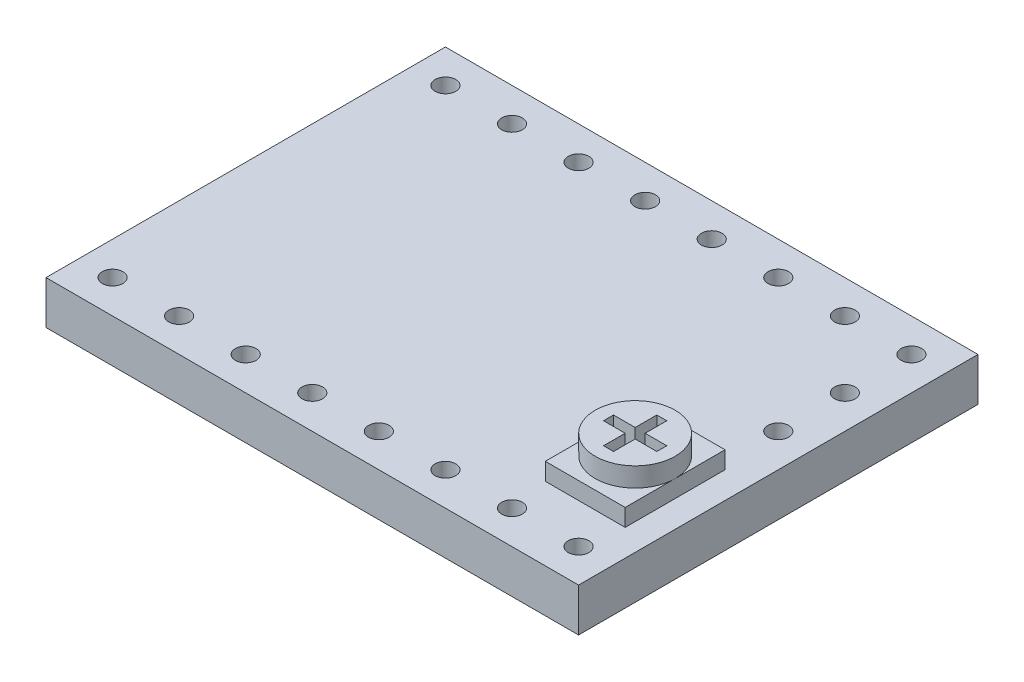
SolidWorks part; units mm, degrees
ref_plane "Front Plane" through (0, 0, 0) normal (0, 0, 1) x (1, 0, 0)
ref_plane "Top Plane" through (0, 0, 0) normal (0, 1, 0) x (1, 0, 0)
ref_plane "Right Plane" through (0, 0, 0) normal (1, 0, 0) x (0, 0, -1)
sketch "Sketch1" plane through (0, 0, 0) normal (0, 1, 0) x (1, 0, 0)
  line L1 (-10.16, -7.62) -> (10.16, -7.62)
  line L2 (-10.16, -7.62) -> (-10.16, 7.62)
  line L3 (-10.16, 7.62) -> (10.16, 7.62)
  line L4 (10.16, -7.62) -> (10.16, 7.62)
  line L5 (-10.16, -7.62) -> (10.16, 7.62) construction
  line L6 (-10.16, 7.62) -> (10.16, -7.62) construction
  point P0 (0, 0)
  dimension "D1" = 20.32
  dimension "D2" = 15.24
extrude "Boss-Extrude1" add sketch "Sketch1" along normal blind 1.651
sketch "Sketch3" plane through (0, 1.651, 0) normal (0, 1, 0) x (1, 0, 0)
  line L0 (10.16, -7.62) -> (10.16, 7.62) construction
  line L1 (6.096, -4.826) -> (9.144, -4.826)
  line L2 (6.096, -4.826) -> (6.096, -1.016)
  line L3 (6.096, -1.016) -> (9.144, -1.016)
  line L4 (9.144, -4.826) -> (9.144, -1.016)
  line L5 (-10.16, -7.62) -> (10.16, -7.62) construction
  dimension "D1" = 3.048
  dimension "D2" = 1.016
  dimension "D3" = 2.794
  dimension "D4" = 3.81
extrude "Boss-Extrude3" add sketch "Sketch3" along normal offset from surface (0.6604 mm away) 2.3114 up to face at (0, 0, 0)
sketch "Sketch4" plane through (0, 2.3114, 0) normal (0, 1, 0) x (1, 0, 0)
  line L0 (6.096, -4.826) -> (9.144, -1.016) construction
  line L1 (7.8105, -2.7305) -> (8.636, -2.7305)
  line L2 (7.4295, -3.937) -> (7.8105, -3.937)
  line L3 (7.4295, -3.937) -> (7.4295, -3.1115)
  line L4 (7.4295, -1.905) -> (7.8105, -1.905)
  line L5 (7.8105, -3.937) -> (7.8105, -3.1115)
  line L6 (7.4295, -3.937) -> (7.8105, -1.905) construction
  line L7 (7.4295, -1.905) -> (7.8105, -3.937) construction
  line L8 (6.604, -2.7305) -> (7.4295, -2.7305)
  line L9 (6.604, -2.7305) -> (6.604, -3.1115)
  line L10 (6.604, -3.1115) -> (7.4295, -3.1115)
  line L11 (8.636, -2.7305) -> (8.636, -3.1115)
  line L12 (6.604, -2.7305) -> (8.636, -3.1115) construction
  line L13 (6.604, -3.1115) -> (8.636, -2.7305) construction
  line L14 (7.8105, -2.7305) -> (7.8105, -1.905)
  line L15 (7.8105, -3.1115) -> (8.636, -3.1115)
  line L16 (7.4295, -2.7305) -> (7.4295, -1.905)
  circle A0 centre (7.62, -2.921) radius 1.524
  dimension "D1" = 3.048
  dimension "D2" = 0.381
  dimension "D3" = 2.032
extrude "Boss-Extrude4" add sketch "Sketch4" along normal offset from surface (0.7366 mm away) 3.048 up to face at (0, 0, 0)
sketch "Sketch7" plane through (0, 1.651, 0) normal (0, 1, 0) x (1, 0, 0)
  line L0 (-10.16, 7.62) -> (-10.16, -7.62) construction
  line L1 (-10.16, -7.62) -> (10.16, -7.62) construction
  circle A0 centre (-8.89, -6.35) radius 0.3937
  dimension "D1" = 0.7874
  dimension "D2" = 1.27
  dimension "D3" = 1.27
extrude "Cut-Extrude2" cut sketch "Sketch7" against normal through all
pattern_linear "LPattern2" count 8 spacing 2.54 along (1, 0, 0) count 2 spacing 12.7 along (0, 0, -1) of "Cut-Extrude2"
sketch "Sketch8" plane through (0, 1.651, 0) normal (0, 1, 0) x (1, 0, 0)
  line L0 (8.89, 6.35) -> (8.89, 1.27) construction
  circle A0 centre (8.89, 3.81) radius 0.3937
  circle A1 centre (8.89, 1.27) radius 0.3937
  circle A2 centre (8.89, 6.35) radius 0.3937 construction
  dimension "D1" = 2.54
  dimension "D2" = 2.54
extrude "Cut-Extrude3" cut sketch "Sketch8" against normal up to next
equation "\"D2@Sketch8\"=\"D1@Sketch8\""
